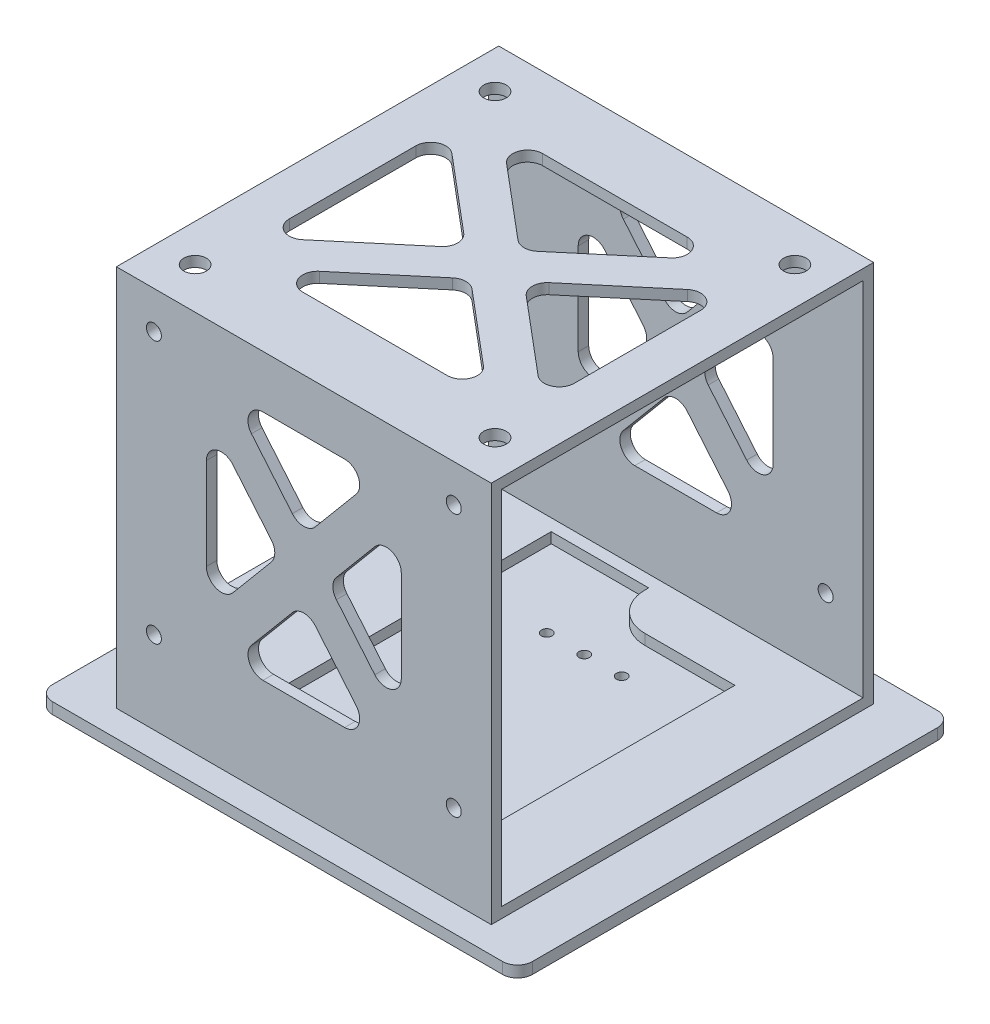
SolidWorks part; units mm, degrees
ref_plane "Plano frontal" through (0, 0, 0) normal (0, 0, 1) x (1, 0, 0)
ref_plane "Plano superior" through (0, 0, 0) normal (0, 1, 0) x (1, 0, 0)
ref_plane "Plano direito" through (0, 0, 0) normal (1, 0, 0) x (0, 0, -1)
sketch "Esboço1" plane through (0, 0, 0) normal (1, 0, 0) x (0, -1, 0)
  line L1 (25.5, 25.5) -> (-25.5, 25.5)
  line L2 (25.5, 25.5) -> (25.5, -25.5)
  line L3 (25.5, -25.5) -> (-25.5, -25.5)
  line L4 (-25.5, 25.5) -> (-25.5, -25.5)
  line L5 (25.5, 25.5) -> (-25.5, -25.5) construction
  line L6 (25.5, -25.5) -> (-25.5, 25.5) construction
  line L7 (24.1, 24.1) -> (-24.1, 24.1)
  line L8 (24.1, 24.1) -> (24.1, -24.1)
  line L9 (24.1, -24.1) -> (-24.1, -24.1)
  line L10 (-24.1, 24.1) -> (-24.1, -24.1)
  line L11 (24.1, 24.1) -> (-24.1, -24.1) construction
  line L12 (24.1, -24.1) -> (-24.1, 24.1) construction
  point P0 (0, 0)
  point P6 (0, 0)
  dimension "D1" = 51
  dimension "D2" = 51
  dimension "D3" = 1.4
  dimension "D4" = 1.4
extrude "Ressalto-extrusão1" add sketch "Esboço1" along normal blind 50
sketch "Esboço2" plane through (0, -25.5, 0) normal (0, 1, 0) x (0, 0, 1)
  line L0 (-25.5, 25) -> (25.5, 25) construction
  line L1 (29, 57) -> (-29, 57)
  line L2 (29, 57) -> (29, -7)
  line L3 (29, -7) -> (-29, -7)
  line L4 (-29, 57) -> (-29, -7)
  line L5 (29, 57) -> (-29, -7) construction
  line L6 (29, -7) -> (-29, 57) construction
  line L7 (-25.5, 50) -> (-25.5, 0) construction
  line L8 (25.5, 50) -> (25.5, 0) construction
  point P0 (0, 25)
  point P14 (0, 25)
  dimension "D1" = 64
  dimension "D2" = 58
extrude "Ressalto-extrusão2" add sketch "Esboço2" against normal blind 1.5 separate body
sketch "Esboço3" plane through (0, 25.5, 0) normal (0, -1, 0) x (0, 0, -1)
  line L0 (-25.5, 25) -> (25.5, 25) construction
  line L1 (20, 45) -> (-20, 45) construction
  line L2 (20, 45) -> (20, 5) construction
  line L3 (20, 5) -> (-20, 5) construction
  line L4 (-20, 45) -> (-20, 5) construction
  line L5 (20, 45) -> (-20, 5) construction
  line L6 (20, 5) -> (-20, 45) construction
  line L9 (14.0877, 45.6103) -> (-17.9123, 7.6103)
  line L10 (16, 44) -> (-16, 44)
  line L11 (16, 44) -> (16, 6)
  line L12 (16, 6) -> (-16, 6)
  line L13 (-16, 44) -> (-16, 6)
  line L14 (16, 44) -> (-16, 6) construction
  line L15 (16, 6) -> (-16, 44) construction
  line L16 (17.9123, 7.6103) -> (-14.0877, 45.6103)
  line L17 (17.9123, 42.3897) -> (-14.0877, 4.3897)
  line L18 (14.0877, 4.3897) -> (-17.9123, 42.3897)
  line L19 (25.5, 50) -> (25.5, 0) construction
  line L20 (-25.5, 50) -> (-25.5, 0) construction
  circle A0 centre (-20, 45) radius 1.5
  circle A1 centre (20, 45) radius 1.5
  circle A2 centre (20, 5) radius 1.5
  circle A3 centre (-20, 5) radius 1.5
  point P0 (0, 25)
  point P16 (0, 25)
  dimension "D3" = 3
  dimension "D1" = 40
  dimension "D2" = 40
  dimension "D4" = 38
  dimension "D5" = 32
  dimension "D6" = 2.5
  dimension "D7" = 2.5
extrude "Corte-extrusão1" cut sketch "Esboço3" along normal blind 1.5 contours L17 L11 L16 | L9 L16 L10 | L18 L9 L13 | L18 L12 L17 | A2 | A3 | A0 | A1 region at (38.9604, 25.5, 0) region at (25, 25.5, 11.7561) region at (25, 25.5, -11.7561) region at (11.0396, 25.5, 0) region at (45, 25.5, 20) region at (45, 25.5, -20) region at (5, 25.5, -20) region at (5, 25.5, 20)
fillet "Filete1" radius 2 12 edges at (44, 24.8, -12.7316) (44, 24.8, 12.7316) (40.1188, 24.8, 16) (6, 24.8, 12.7316) (6, 24.8, -12.7316) (9.8812, 24.8, -16) (40.1188, 24.8, -16) (21.1188, 24.8, 0) (28.8812, 24.8, 0) (25, 24.8, -3.2684) (25, 24.8, 3.2684) (9.8812, 24.8, 16)
sketch "Esboço4" plane through (0, 0, -25.5) normal (0, 0, 1) x (1, 0, 0)
  line L0 (25.5, 3) -> (-25.5, 3) construction
  line L1 (5, -14.5) -> (45, -14.5) construction
  line L2 (5, -14.5) -> (5, 20.5) construction
  line L3 (5, 20.5) -> (45, 20.5) construction
  line L4 (45, -14.5) -> (45, 20.5) construction
  line L5 (5, -14.5) -> (45, 20.5) construction
  line L6 (5, 20.5) -> (45, -14.5) construction
  line L10 (38, 18.5) -> (12, 18.5)
  line L11 (38, 18.5) -> (38, -12.5)
  line L12 (38, -12.5) -> (12, -12.5)
  line L13 (12, 18.5) -> (12, -12.5)
  line L14 (38, 18.5) -> (12, -12.5) construction
  line L15 (38, -12.5) -> (12, 18.5) construction
  line L16 (36.0845, 20.1065) -> (10.0845, -10.8935)
  line L17 (39.9155, -10.8935) -> (13.9155, 20.1065)
  line L18 (39.9155, 16.8935) -> (13.9155, -14.1065)
  line L19 (36.0845, -14.1065) -> (10.0845, 16.8935)
  line L20 (50, 25.5) -> (0, 25.5) construction
  line L22 (25, -25.5) -> (25, 25.5) construction
  line L23 (-7, -25.5) -> (57, -25.5) construction
  circle A0 centre (5, 20.5) radius 1
  circle A1 centre (45, 20.5) radius 1
  circle A2 centre (45, -14.5) radius 1
  circle A3 centre (5, -14.5) radius 1
  point P0 (25, 3)
  point P15 (25, 3)
  dimension "D4" = 2
  dimension "D1" = 40
  dimension "D2" = 35
  dimension "D3" = 5
  dimension "D5" = 7
  dimension "D6" = 26
  dimension "D7" = 2.5
  dimension "D8" = 2.5
extrude "Corte-extrusão2" cut sketch "Esboço4" along normal through all contours L19 L12 L18 | L19 L16 L13 | L16 L17 L10 | L18 L11 L17 | A2 | A3 | A0 | A1 region at (25, 14.6301, -25.5) region at (34.7543, 3, -25.5) region at (15.2457, 3, -25.5) region at (25, -8.6301, -25.5) region at (5, 20.5, -25.5) region at (45, 20.5, -25.5) region at (45, -14.5, -25.5) region at (5, -14.5, -25.5)
fillet "Filete2" radius 2 24 edges at (38, -8.6096, 24.8) (38, 14.6096, 24.8) (34.7371, 18.5, 24.8) (15.2629, 18.5, 24.8) (12, -8.6096, 24.8) (15.2629, -12.5, 24.8) (34.7371, -12.5, 24.8) (21.7371, 3, 24.8) (28.2629, 3, 24.8) (25, 6.8904, 24.8) (34.7371, -12.5, -24.8) (38, -8.6096, -24.8) (15.2629, -12.5, -24.8) (12, -8.6096, -24.8) (38, 14.6096, -24.8) (34.7371, 18.5, -24.8) (12, 14.6096, -24.8) (15.2629, 18.5, -24.8) (25, -0.8904, -24.8) (28.2629, 3, -24.8) (21.7371, 3, -24.8) (25, 6.8904, -24.8) (12, 14.6096, 24.8) (25, -0.8904, 24.8)
sketch "Esboço5" plane through (0, -25.5, 0) normal (0, -1, 0) x (0, 0, -1)
  line L1 (-25.5, 0) -> (25.5, 0)
  line L2 (-25.5, 0) -> (-25.5, 50)
  line L3 (-25.5, 50) -> (25.5, 50)
  line L4 (25.5, 0) -> (25.5, 50)
extrude "Ressalto-extrusão3" [suppressed] add sketch "Esboço5" along normal blind 9 from offset 1
sketch "Esboço6" plane through (0, 24.1, 0) normal (0, -1, 0) x (0, 0, -1)
  line L0 (-17, 40) -> (17, 40)
  line L1 (17, 40) -> (17, 28)
  line L2 (-17, 40) -> (-17, 28)
  line L3 (22, 23) -> (22.5, 23)
  line L4 (22.5, 23) -> (22.5, 10)
  line L5 (22.5, 10) -> (-22.5, 10)
  line L6 (-22.5, 10) -> (-22.5, 23)
  line L7 (-22.5, 23) -> (-22, 23)
  line L8 (24.1, 50) -> (-24.1, 50) construction
  line L9 (24.1, 0) -> (-24.1, 0) construction
  arc A0 (17, 28) -> (22, 23) centre (22, 28) ccw
  arc A1 (-17, 28) -> (-22, 23) centre (-22, 28) cw
  point P12 (0, 40)
  dimension "D6" = 5
  dimension "D1" = 10
  dimension "D2" = 34
  dimension "D3" = 45
  dimension "D4" = 10
  dimension "D5" = 27
extrude "Corte-extrusão3" cut sketch "Esboço6" against normal up to surface (-49.6 mm away) up to face at (25, -25.5, 0)
sketch "Esboço7" plane through (0, -27, 0) normal (0, -1, 0) x (1, 0, 0)
  line L0 (20, 11.9) -> (30, 11.9) construction
  line L1 (20, -11.9) -> (30, -11.9) construction
  line L3 (-7, -29) -> (-7, 29) construction
  circle A0 centre (20, 11.9) radius 0.7
  circle A1 centre (30, 11.9) radius 0.7
  circle A2 centre (30, -11.9) radius 0.7
  circle A3 centre (20, -11.9) radius 0.7
  circle A4 centre (25, -11.9) radius 0.7
  circle A5 centre (25, 11.9) radius 0.7
  dimension "D3" = 1.4
  dimension "D1" = 23.8
  dimension "D2" = 11.9
  dimension "D4" = 10
  dimension "D5" = 32
  dimension "D6" = 32
extrude "Corte-extrusão4" cut sketch "Esboço7" against normal blind 10
fillet "Filete3" radius 2 4 edges at (-7, -26.25, 29) (-7, -26.25, -29) (57, -26.25, -29) (57, -26.25, 29)
equation "\"D2@Esboço7\"=\"D1@Esboço7\"/2"
equation "\"D6@Esboço7\"=\"D5@Esboço7\""
